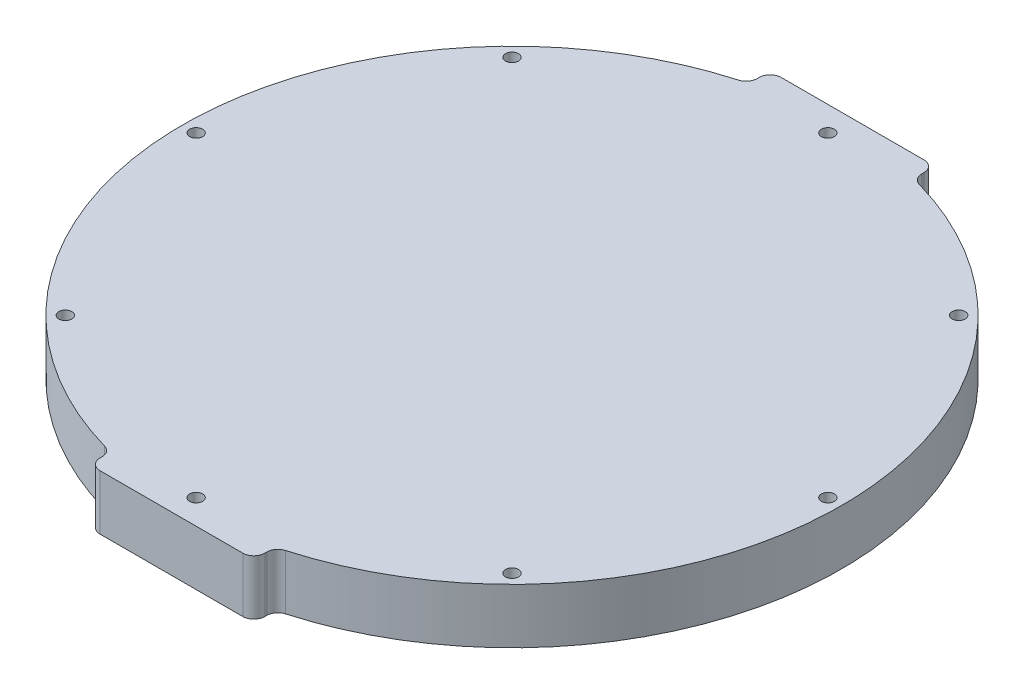
SolidWorks part; units mm, degrees
material "1060 Alloy"
ref_plane "Front Plane" through (0, 0, 0) normal (0, 0, 1) x (1, 0, 0)
ref_plane "Top Plane" through (0, 0, 0) normal (0, 1, 0) x (1, 0, 0)
ref_plane "Right Plane" through (0, 0, 0) normal (1, 0, 0) x (0, 0, -1)
sketch "Sketch2" plane through (0, 0, 0) normal (0, 1, 0) x (1, 0, 0)
  circle A0 centre (0, 0) radius 76.2
extrude "Boss-Extrude1" add sketch "Sketch2" along normal blind 12.7
sketch "Sketch3" plane through (0, 0, 0) normal (0, 0, 1) x (1, 0, 0)
  line L0 (0, 0) -> (-19.05, 0)
  line L1 (-19.05, 0) -> (-19.05, 12.7)
  line L2 (-19.05, 12.7) -> (19.05, 12.7)
  line L3 (19.05, 12.7) -> (19.05, 0)
  line L4 (0, 0) -> (19.05, 0)
extrude "Boss-Extrude2" add sketch "Sketch3" along normal blind 78.74 and the other way blind 78.74
fillet "Fillet1" radius 2.54 8 edges at (19.05, 6.35, 73.7803) (19.05, 6.35, 78.74) (-19.05, 6.35, 73.7803) (-19.05, 6.35, 78.74) (-19.05, 6.35, -73.7803) (-19.05, 6.35, -78.74) (19.05, 6.35, -73.7803) (19.05, 6.35, -78.74)
sketch "Sketch4" plane through (0, 12.7, 0) normal (0, 1, 0) x (1, 0, 0)
  circle A0 centre (73.025, 0) radius 1.5011
  circle A1 centre (51.6365, -51.6365) radius 1.5011
  circle A2 centre (0, -73.025) radius 1.5011
  circle A3 centre (-51.6365, -51.6365) radius 1.5011
  circle A4 centre (-73.025, 0) radius 1.5011
  circle A5 centre (-51.6365, 51.6365) radius 1.5011
  circle A6 centre (0, 73.025) radius 1.5011
  circle A7 centre (51.6365, 51.6365) radius 1.5011
  point P18 (0, 0)
  dimension "D1" = 8
extrude "Cut-Extrude1" cut sketch "Sketch4" against normal through all
